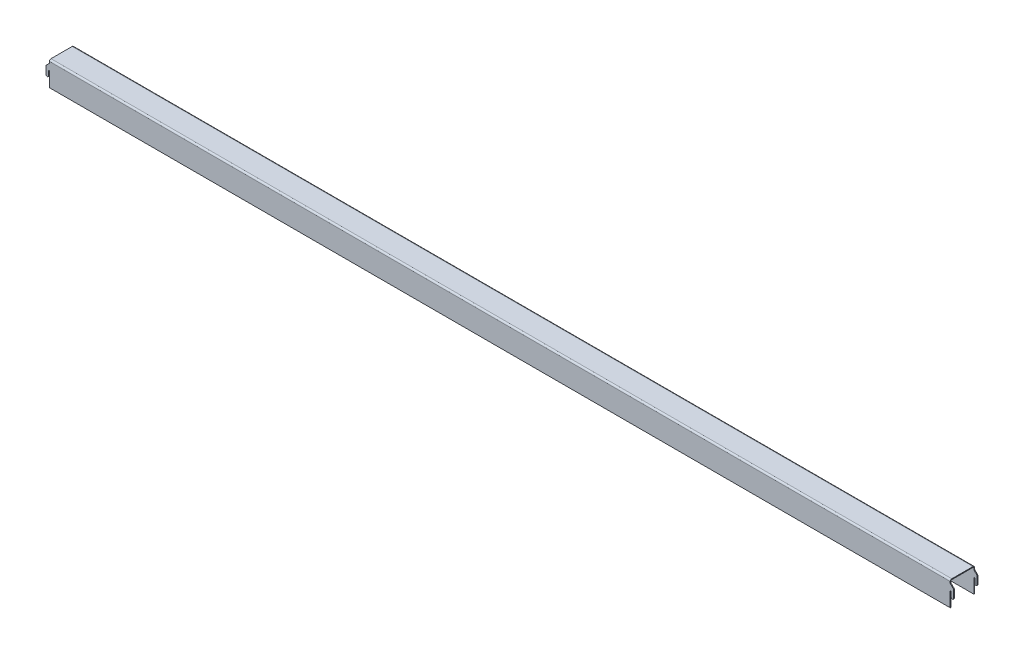
SolidWorks part; units mm, degrees
note: The reader was unsure of these and kept them because the rebuilt part matched: flange length of "Edge-Flange1".
material "5052-H32"
ref_plane "Front Plane" through (0, 0, 0) normal (0, 0, 1) x (1, 0, 0)
ref_plane "Top Plane" through (0, 0, 0) normal (0, 1, 0) x (1, 0, 0)
ref_plane "Right Plane" through (0, 0, 0) normal (1, 0, 0) x (0, 0, -1)
sketch "Sketch2" plane through (0, 0, 0) normal (0, 1, 0) x (1, 0, 0)
  line L1 (1173.861, -31.75) -> (-1173.861, -31.75)
  line L2 (1173.861, -31.75) -> (1173.861, 31.75)
  line L3 (1173.861, 31.75) -> (-1173.861, 31.75)
  line L4 (-1173.861, -31.75) -> (-1173.861, 31.75)
  line L5 (1173.861, -31.75) -> (-1173.861, 31.75) construction
  line L6 (1173.861, 31.75) -> (-1173.861, -31.75) construction
  point P0 (0, 0)
  dimension "D1" = 2347.722
  dimension "D2" = 63.5
base flange "Base-Flange1" sketch "Sketch2" thickness 2.0574 reverse thickness direction no parameters "D1"=2.032
edge flange "Edge-Flange1" sketch "Sketch9" flange angle 90 flange length 63.5 flange position material inside bend radius 2.032 thickness 2.0574 relief rectangular parameters "D6"=10
sketch "Sketch9" plane through (0, -2.0574, -31.75) normal (0, 0, 1) x (-1, 0, 0)
  line L0 (1176.401, 23.3426) -> (1173.861, 23.3426)
  line L2 (-1173.861, 0) -> (-1173.861, 6.35)
  line L3 (-1173.861, 61.4426) -> (1173.861, 61.4426)
  line L4 (1173.861, 61.4426) -> (1173.861, 23.3426)
  line L5 (1173.861, 0) -> (-1173.861, 0) construction
  line L6 (1173.861, 0) -> (-1173.861, 0)
  line L7 (-1173.861, -2.0574) -> (1173.861, -2.0574) construction
  line L8 (-1173.861, 23.3426) -> (-1173.861, 61.4426)
  line L9 (-1173.861, 6.35) -> (-1182.751, 15.24)
  line L10 (-1182.751, 15.24) -> (-1182.751, 36.0426)
  line L11 (-1176.401, 36.0426) -> (-1176.401, 23.3426)
  line L12 (0, -159.78) -> (0, 155.6652) construction
  line L13 (-1176.401, 23.3426) -> (-1173.861, 23.3426)
  line L14 (1176.401, 36.0426) -> (1176.401, 23.3426)
  line L15 (1182.751, 15.24) -> (1182.751, 36.0426)
  line L16 (1173.861, 6.35) -> (1182.751, 15.24)
  line L17 (1173.861, 6.35) -> (1173.861, 0)
  line L18 (-1179.576, 39.2176) -> (-1179.576, 12.065) construction
  arc A0 (-1182.751, 36.0426) -> (-1176.401, 36.0426) centre (-1179.576, 36.0426) cw
  arc A1 (1182.751, 36.0426) -> (1176.401, 36.0426) centre (1179.576, 36.0426) ccw
  point P16 (0, -2.0574)
  dimension "D2" = 2.54
  dimension "D7" = 38.1
  dimension "D1" = 63.5
  dimension "D3" = 6.35
  dimension "D4" = 25.4
  dimension "D5" = 135
  dimension "D6" = 6.35
bend "EdgeBend1" bend radius 2.032 bend angle 90 parameters "D5"=1
mirror "Mirror1" about plane through (0, 0, 0) normal (0, 0, 1) of "Edge-Flange1"
bend "MirrorBend1" bend radius 2.032 bend angle 90 parameters "D5"=2
sketch "Bend-Lines1" [suppressed] plane through (0, 0, 0) normal (0, 1, 0) x (1, 0, 0)
sketch "Bounding-Box1" [suppressed] plane through (0, 0, 0) normal (0, 1, 0) x (1, 0, 0)
sheet metal parameters "Sheet-Metal1" thickness 2.0574 parameters "D1"=2.032
flat pattern "Flat-Pattern1" [suppressed]
sketch "Bend-Lines2" plane through (0, 0, 0) normal (0, 1, 0) x (1, 0, 0)
sketch3d "Bounding-Box2" [suppressed]
  line L0 (-1193.8, -31.75, 0) -> (1193.8, -31.75, 0) construction
  line L1 (-1193.8, 31.75, 0) -> (1193.8, 31.75, 0) construction
  line L2 (-1193.8, -31.75, 0) -> (-1193.8, 31.75, 0) construction
  line L3 (1193.8, -31.75, 0) -> (1193.8, 31.75, 0) construction
sheet metal parameters "Sheet-Metal2" thickness 2.0574 parameters "D1"=2.032
flat pattern "Flat-Pattern1"
sketch "Bend-Lines2" plane through (0, 0, 0) normal (0, 1, 0) x (1, 0, 0)
  line L0 (1193.8, 30.1107) -> (-1193.8, 30.1107) construction
  line L1 (1193.8, 30.1107) -> (-1193.8, 30.1107) construction
sketch3d "Bounding-Box2" [suppressed]
  line L0 (1202.69, -31.75, 0) -> (-1202.69, -31.75, 0) construction
  line L1 (1202.69, 91.9715, 0) -> (-1202.69, 91.9715, 0) construction
  line L2 (1202.69, -31.75, 0) -> (1202.69, 91.9715, 0) construction
  line L3 (-1202.69, -31.75, 0) -> (-1202.69, 91.9715, 0) construction
bend of the flat pattern "Flatten-<EdgeBend1>1"
sheet metal parameters "Sheet-Metal3" thickness 2.0574 parameters "D1"=2.032
flat pattern "Flat-Pattern1"
sketch "Bend-Lines2" plane through (0, 0, 0) normal (0, 1, 0) x (1, 0, 0)
  line L0 (1173.861, 30.0645) -> (-1173.861, 30.0645) construction
  line L1 (1173.861, 30.0645) -> (-1173.861, 30.0645) construction
  line L2 (-1173.861, -30.0645) -> (1173.861, -30.0645) construction
  line L3 (-1173.861, -30.0645) -> (1173.861, -30.0645) construction
sketch3d "Bounding-Box2" [suppressed]
  line L0 (-1182.751, -91.8771, 0) -> (1182.751, -91.8789, 0) construction
  line L1 (-1182.7509, 91.8789, 0) -> (1182.7511, 91.8771, 0) construction
  line L2 (-1182.751, -91.8771, 0) -> (-1182.7509, 91.8789, 0) construction
  line L3 (1182.751, -91.8789, 0) -> (1182.7511, 91.8771, 0) construction
bend of the flat pattern "Flatten-<EdgeBend1>1"
bend of the flat pattern "Flatten-<MirrorBend1>1"
